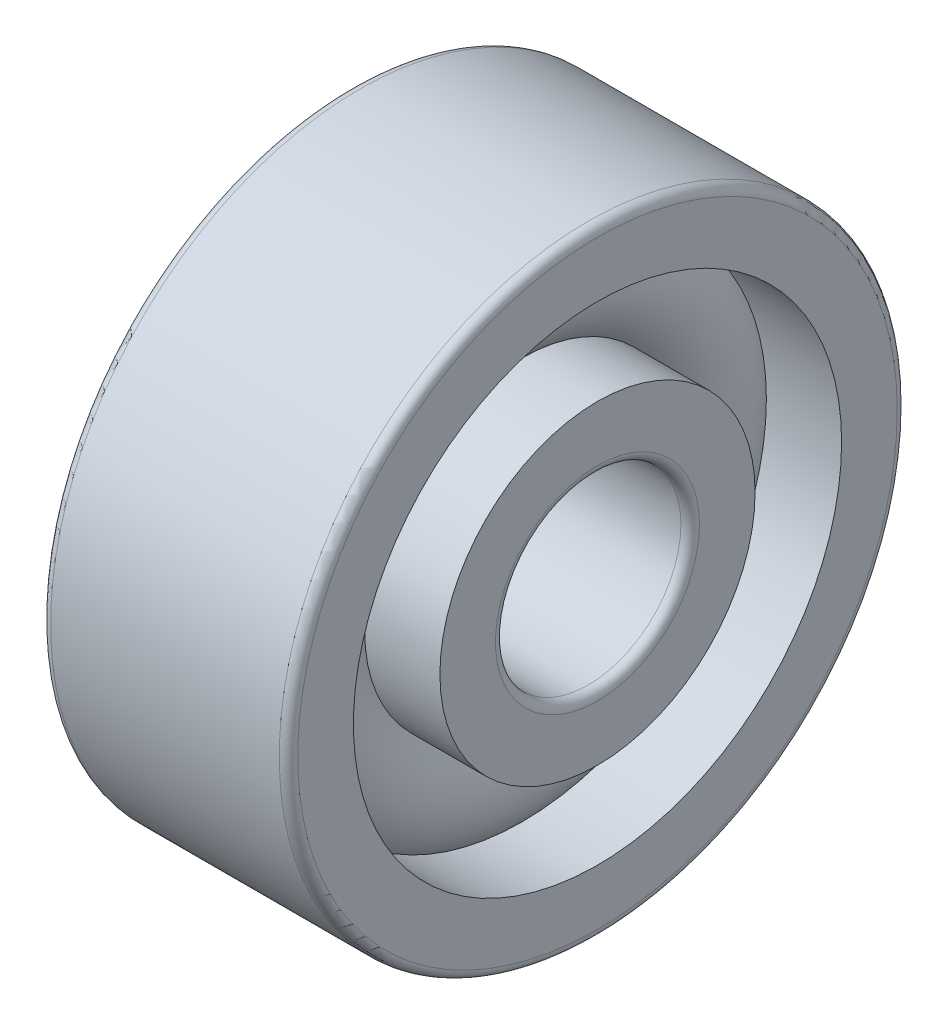
SolidWorks part; units mm, degrees
ref_plane "Plane1" through (0, 0, 0) normal (0, 0, 1) x (1, 0, 0)
ref_plane "Plane2" through (0, 0, 0) normal (0, 1, 0) x (1, 0, 0)
ref_plane "Plane3" through (0, 0, 0) normal (1, 0, 0) x (0, 0, -1)
sketch "Clipboard" plane through (0, 0, 0) normal (0, 0, 1) x (1, 0, 0)
  line L0 (-10, 0) -> (10, 0) construction
  line L1 (0, 0) -> (22.3471, -0.7804)
  line L2 (0, 0) -> (3.248, 0.1134)
  line L3 (0, 0) -> (22.3471, -0.7804)
  line L4 (0, 0) -> (-22.3573, -0.3902)
  dimension "BallCLRad" = 3.25
  dimension "Count" = 2
  dimension "Show_count" = 2
  dimension "Max_count" = 2
  dimension "Min_count" = 1
sketch "CagSpiSke" plane through (0, 0, 0) normal (0, 0, 1) x (1, 0, 0)
  line L0 (0.105, 3.075) -> (0.105, 3.425)
  line L1 (0.105, 3.425) -> (-0.105, 3.425)
  line L2 (-0.105, 3.425) -> (-0.105, 3.075)
  line L3 (-0.105, 3.075) -> (0.105, 3.075)
  line L4 (-20.6375, 0) -> (20.6375, 0) construction
  line L5 (0, 0) -> (0, 23.7692) construction
  dimension "Thickness" = 0.21
  dimension "OD" = 6.85
  dimension "ID" = 6.15
revolve "CageSpine" add sketch "CagSpiSke" angle 0.001 about L4 reverse direction yes
ref_axis "Axis1" through (-50, 0, 0) along (1, 0, 0)
sketch "CagBalSke" plane through (0, 0, 0) normal (0, 0, 1) x (1, 0, 0)
  line L0 (-1.155, 3.25) -> (1.155, 3.25)
  line L1 (-1.905, 3.25) -> (1.905, 3.25) construction
  line L2 (-10, 0) -> (10, 0) construction
  line L3 (0, 0) -> (0, 24) construction
  arc A0 (1.155, 3.25) -> (-1.155, 3.25) centre (0, 3.25) cw
  dimension "CageWallOD" = 2.31
  dimension "BallCLRad" = 3.25
revolve "CageBall" [suppressed] add sketch "CagBalSke" angle 360 about L1 reverse direction yes
pattern_circular "CageBalls" [suppressed] count 2 every 180 about axis through (-50, 0, 0) along (1, 0, 0)
sketch "CagTrmODSke" plane through (0, 0, 0) normal (0, 0, 1) x (1, 0, 0)
  line L0 (1.156, 3.425) -> (1.156, 4.406)
  line L1 (1.156, 4.406) -> (-1.156, 4.406)
  line L2 (-1.156, 4.406) -> (-1.156, 3.425)
  line L3 (-1.156, 3.425) -> (1.156, 3.425)
  line L4 (-20.6375, 0) -> (20.6375, 0) construction
  line L5 (0, 0) -> (0, 25) construction
  dimension "Width" = 2.312
  dimension "ID" = 6.85
  dimension "OD" = 8.812
revolve "CageTrimOD" [suppressed] cut sketch "CagTrmODSke" angle 360 about L4 reverse direction yes
sketch "CagTrmIDSke" plane through (0, 0, 0) normal (0, 0, 1) x (1, 0, 0)
  line L0 (1.156, 2.096) -> (1.156, 3.075)
  line L1 (1.156, 3.075) -> (-1.156, 3.075)
  line L2 (-1.156, 3.075) -> (-1.156, 2.096)
  line L3 (-1.156, 2.096) -> (1.156, 2.096)
  line L4 (-20.6375, 0) -> (20.6375, 0) construction
  line L5 (0, 0) -> (0, 25) construction
  dimension "ID" = 4.192
  dimension "OD" = 6.15
  dimension "Width" = 2.312
revolve "CageTrimID" [suppressed] cut sketch "CagTrmIDSke" angle 360 about L4 reverse direction yes
sketch "BalSimSke" plane through (0, 0, 0) normal (0, 0, 1) x (1, 0, 0)
  line L0 (-10, 0) -> (10, 0) construction
  line L1 (-10, 3.25) -> (10, 3.25) construction
  line L2 (0, 0) -> (0, 23) construction
  circle A0 centre (0, 3.25) radius 1.05
  dimension "Ball_diameter" = 2.1
  dimension "BallCLRad" = 3.25
revolve "BallsSimplified" add sketch "BalSimSke" angle 360 about L0
sketch "BalDetSke" plane through (0, 0, 0) normal (0, 0, 1) x (1, 0, 0)
  line L0 (-1.05, 3.25) -> (1.05, 3.25)
  line L1 (-1.905, 3.25) -> (1.905, 3.25) construction
  line L2 (0, 0) -> (0, 25) construction
  arc A0 (1.05, 3.25) -> (-1.05, 3.25) centre (0, 3.25) cw
  dimension "Ball_diameter" = 2.1
  dimension "BallCLRad" = 3.25
revolve "BallDetailed" [suppressed] add sketch "BalDetSke" angle 360 about L1 reverse direction yes
sketch "InnRacSke" plane through (0, 0, 0) normal (0, 0, 1) x (1, 0, 0)
  line L0 (-0.7487, 2.55) -> (-2, 2.55)
  line L1 (-2, 2.55) -> (-2, 1.65)
  line L2 (-1.85, 1.5) -> (1.85, 1.5)
  line L3 (2, 1.65) -> (2, 2.55)
  line L4 (2, 2.55) -> (0.7487, 2.55)
  line L5 (-20.6375, 0) -> (20.6375, 0) construction
  line L6 (0, 0) -> (0, 30) construction
  arc A0 (-2, 1.65) -> (-1.85, 1.5) centre (-1.85, 1.65) ccw
  arc A1 (1.85, 1.5) -> (2, 1.65) centre (1.85, 1.65) ccw
  arc A2 (0.7487, 2.55) -> (-0.7487, 2.55) centre (0, 3.25) cw
  dimension "Fillet_radius" = 0.15
  dimension "Ball_diameter" = 2.05
  dimension "ID" = 3
  dimension "OD" = 5.1
  dimension "Width" = 4
  dimension "BallCLRad" = 3.25
revolve "InnerRace" add sketch "InnRacSke" angle 360 about L5 reverse direction yes
sketch "OutRacSke" plane through (0, 0, 0) normal (0, 0, 1) x (1, 0, 0)
  line L0 (-0.7487, 3.95) -> (-2, 3.95)
  line L1 (-2, 3.95) -> (-2, 4.85)
  line L2 (-1.85, 5) -> (1.85, 5)
  line L3 (2, 4.85) -> (2, 3.95)
  line L4 (2, 3.95) -> (0.7487, 3.95)
  line L5 (-20.6375, 0) -> (20.6375, 0) construction
  line L6 (0, 0) -> (0, 30) construction
  arc A0 (-2, 4.85) -> (-1.85, 5) centre (-1.85, 4.85) cw
  arc A1 (1.85, 5) -> (2, 4.85) centre (1.85, 4.85) cw
  arc A2 (0.7487, 3.95) -> (-0.7487, 3.95) centre (0, 3.25) ccw
  dimension "Fillet_radius" = 0.15
  dimension "Ball_diameter" = 2.05
  dimension "OD" = 10
  dimension "ID" = 7.9
  dimension "Width" = 4
  dimension "BallCLRad" = 3.25
revolve "OuterRace" add sketch "OutRacSke" angle 360 about L5 reverse direction yes
pattern_circular "BallsDetailed" [suppressed] count 2 every 180 about axis through (-50, 0, 0) along (1, 0, 0)
equation "\"BallCLRad@Clipboard\" = ( \"OD@OutRacSke\" + \"ID@InnRacSke\" ) / 4"
equation "\"BallCLRad@BalSimSke\" = \"BallCLRad@Clipboard\""
equation "\"BallCLRad@BalDetSke\" = \"BallCLRad@Clipboard\""
equation "\"BallCLRad@InnRacSke\" = \"BallCLRad@Clipboard\""
equation "\"BallCLRad@OutRacSke\" = \"BallCLRad@Clipboard\""
equation "\"Ball_diameter@InnRacSke\" = \"Ball_diameter@BalDetSke\" - 0.05"
equation "\"Ball_diameter@OutRacSke\" = \"Ball_diameter@BalDetSke\" - 0.05"
equation "\"Ball_diameter@BalSimSke\" = \"Ball_diameter@BalDetSke\""
equation "\"Width@OutRacSke\" = \"Width@InnRacSke\""
equation "\"Fillet_radius@OutRacSke\" = \"Fillet_radius@InnRacSke\""
equation "\"Max_count@Clipboard\" = int( 3.14159265 / atn(( \"Ball_diameter@BalDetSke\" / 2) / sqr( \"BallCLRad@Clipboard\"  *  \"BallCLRad@Clipboard\" - ( \"Ball_diameter@BalDetSke\" / 2) *  ( \"Ball_diameter@BalDetSke\" / 2))))"
equation "\"Max_count@Clipboard\" = ((sgn( \"Max_count@Clipboard\" - \"Count@Clipboard\" )-1)*( \"Max_count@Clipboard\" - \"Count@Clipboard\" ))/-2+ \"Count@Clipboard\""
equation "\"Count@BallsDetailed\" = int( \"Show_count@Clipboard\" ) "
equation "\"Count@BallsDetailed\" = ((sgn( \"Count@BallsDetailed\" - \"Max_count@Clipboard\" )-1)*( \"Count@BallsDetailed\" - \"Max_count@Clipboard\" ))/-2+ \"Max_count@Clipboard\""
equation "\"Count@BallsDetailed\" = ((sgn( \"Count@BallsDetailed\" - \"Min_count@Clipboard\" )+1)*( \"Count@BallsDetailed\" - \"Min_count@Clipboard\"))/2 +\"Min_count@Clipboard\""
equation "\"Angle@BallsDetailed\" = 360.0 / \"Max_count@Clipboard\""
equation "\"BallCLRad@CagBalSke\" = \"BallCLRad@Clipboard\""
equation "\"Count@CageBalls\" = \"Count@BallsDetailed\""
equation "\"Angle@CageBalls\" = \"Angle@BallsDetailed\""
equation "\"Angle@CageSpine\" =  \"Angle@CageBalls\" * ( \"Count@CageBalls\" -1 + int( \"Count@CageBalls\" / \"Max_count@Clipboard\" ) )  + 0.001 -  int( \"Count@CageBalls\" / \"Max_count@Clipboard\" ) * 0.001"
equation "\"Angle@CageSpine\" =  \"Angle@CageSpine\" * int( \"Min_count@Clipboard\" / 2) + int(1 / \"Min_count@Clipboard\")  * 0.001"
equation "\"CageWallOD@CagBalSke\" =  \"Ball_diameter@BalDetSke\" * 1.1"
equation "\"Thickness@CagSpiSke\" =  \"Ball_diameter@BalDetSke\" * 0.1"
equation "\"OD@CagTrmODSke\" = \"BallCLRad@Clipboard\" * 2 + \"CageWallOD@CagBalSke\" + 0.002"
equation "\"ID@CagTrmODSke\" = \"BallCLRad@Clipboard\" * 2 + \"Ball_diameter@BalDetSke\" / 6"
equation "\"OD@CagTrmIDSke\" = \"BallCLRad@Clipboard\" * 2 - \"Ball_diameter@BalDetSke\" / 6"
equation "\"ID@CagTrmIDSke\" = \"BallCLRad@Clipboard\" * 2 - \"CageWallOD@CagBalSke\" + 0.002"
equation "\"OD@CagSpiSke\" = \"ID@CagTrmODSke\""
equation "\"ID@CagSpiSke\" = \"OD@CagTrmIDSke\""
equation "\"Width@CagTrmODSke\" = \"CageWallOD@CagBalSke\" + 0.002"
equation "\"Width@CagTrmIDSke\" = \"CageWallOD@CagBalSke\" + 0.002"
